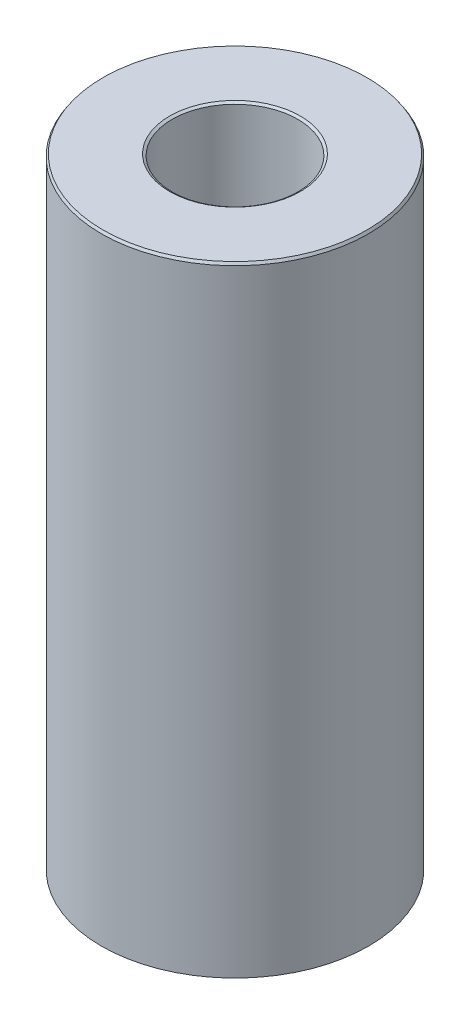
SolidWorks part; units mm, degrees
ref_plane "Front Plane" through (0, 0, 0) normal (0, 0, 1) x (1, 0, 0)
ref_plane "Top Plane" through (0, 0, 0) normal (0, 1, 0) x (1, 0, 0)
ref_plane "Right Plane" through (0, 0, 0) normal (1, 0, 0) x (0, 0, -1)
sketch "Sketch1" plane through (0, 0, 0) normal (0, 1, 0) x (1, 0, 0)
  circle A0 centre (0, 0) radius 27.5
  dimension "SLEEVE_OD" = 55
extrude "Boss-Extrude1" add sketch "Sketch1" along normal blind 127.8382
sketch "Sketch2" plane through (0, 0, 0) normal (0, 1, 0) x (1, 0, 0)
  circle A0 centre (0, 0) radius 12.9499
  dimension "BORE_D" = 25.8999
extrude "Cut-Extrude1" cut sketch "Sketch2" along normal through all
chamfer "Chamfer1" distance 0.5126 angle 32.357 4 edges at (0, 127.8382, 12.9499) (0, 0, 12.9499) (0, 0, 27.5) (0, 127.8382, 27.5) first distance on face at (0, 127.8382, 12.9499) first distance on face at (0, 0, 12.9499) first distance on face at (0, 127.8382, 27.5)
